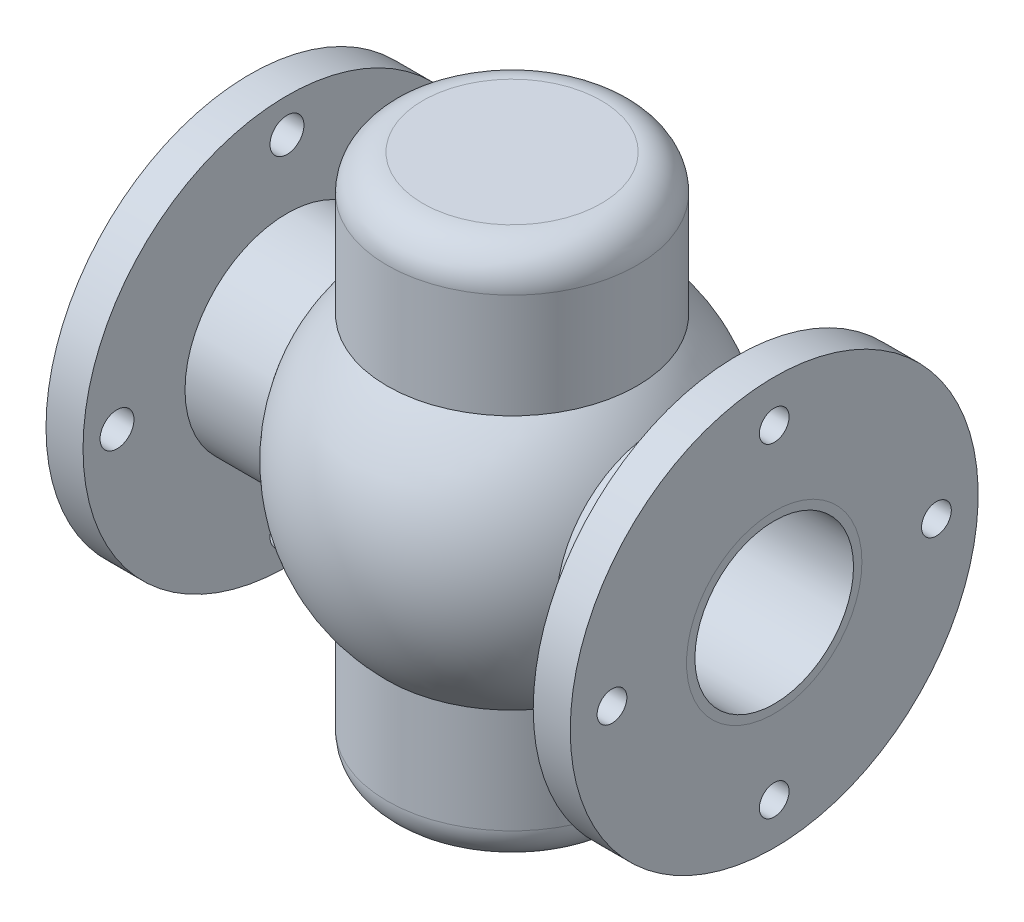
SolidWorks part; units mm, degrees
material "Cast Stainless Steel"
ref_plane "Front" through (0, 0, 0) normal (0, 0, 1) x (1, 0, 0)
ref_plane "Top" through (0, 0, 0) normal (0, 1, 0) x (1, 0, 0)
ref_plane "Right" through (0, 0, 0) normal (1, 0, 0) x (0, 0, -1)
other "Configuration Table"
sketch "Sketch1" plane through (0, 0, 0) normal (1, 0, 0) x (0, 0, -1)
  circle A0 centre (0, 0) radius 57.15
  dimension "D1" = 114.3
extrude "Base-Extrude" add sketch "Sketch1" along normal mid plane 300
sketch "Sketch2" plane through (0, 0, 0) normal (0, 1, 0) x (1, 0, 0)
  circle A0 centre (0, 0) radius 70
  dimension "D1" = 140
extrude "Boss-Extrude1" add sketch "Sketch2" along normal blind 150 and the other way blind 150
sketch "Sketch3" plane through (0, 0, 0) normal (0, 0, 1) x (1, 0, 0)
  line L0 (0, -115.863) -> (0, 215.6893) construction
  line L1 (0, 150) -> (0, -150) construction
  line L2 (0, -100) -> (0, 100)
  arc A0 (0, 100) -> (0, -100) centre (0, 0) cw
  dimension "D1" = 100
revolve "Boss-Revolve1" add sketch "Sketch3" angle 360 about L0
fillet "Fillet1" radius 20 2 edges at (0, -150, 70) (0, 150, 70)
shell "Shell1" [suppressed] thickness 10.5
sketch "Sketch18" plane through (-150, 0, 0) normal (-1, 0, 0) x (0, 0, 1)
  circle A0 centre (0, 0) radius 44.45
  dimension "D1" = 88.9
extrude "Cut-Extrude3" cut sketch "Sketch18" against normal through all
sketch "Sketch5" [suppressed] plane through (0, 0, 0) normal (0, 0, 1) x (1, 0, 0)
  line L0 (190, 198.3801) -> (180, 198.3801)
  line L1 (180, 198.3801) -> (180, 210)
  line L2 (180, 210) -> (185, 210)
  line L3 (180, 210) -> (-180, 210) construction
  line L4 (180, 160) -> (180, 210) construction
  line L5 (0, 0) -> (0, 105.4969) construction
  line L6 (0, 120) -> (0, 71.4143) construction
  arc A0 (190, 198.3801) -> (185, 210) centre (173.9977, 198.3801) ccw
  dimension "D1" = 16.0023
  dimension "D2" = 10
  dimension "D3" = 5
revolve "Boss-Revolve3" [suppressed] add sketch "Sketch5" angle 360 about L5
sketch "Sketch6" plane through (0, 150, 0) normal (0, 1, 0) x (-1, 0, 0)
  circle A0 centre (0, 0) radius 60
  dimension "D1" = 120
extrude "Boss-Extrude2" [suppressed] add sketch "Sketch6" along normal blind 30
sketch "Sketch7" [suppressed] plane through (0, 180, 0) normal (0, 1, 0) x (-1, 0, 0)
  circle A0 centre (0, 0) radius 50
  dimension "D1" = 100
extrude "Boss-Extrude3" [suppressed] add sketch "Sketch7" along normal blind 25
sketch "Sketch8" [suppressed] plane through (0, 205, 0) normal (0, 1, 0) x (-1, 0, 0)
  circle A0 centre (0, 0) radius 35
  dimension "D1" = 70
extrude "Boss-Extrude4" [suppressed] add sketch "Sketch8" along normal blind 10
sketch "Sketch9" [suppressed] plane through (0, 215, 0) normal (0, 1, 0) x (-1, 0, 0)
  circle A0 centre (0, 0) radius 12.5
  dimension "D1" = 25
extrude "Boss-Extrude5" [suppressed] add sketch "Sketch9" along normal blind 35
sketch "hexagon2" [suppressed] plane through (-2.3581, 250, -8.0849) normal (0, 1, 0) x (-1, 0, 0)
  line L0 (17.6378, 8.4916) -> (7.2876, 25.6052)
  line L1 (7.2876, 25.6052) -> (-12.7082, 25.1985)
  line L2 (-12.7082, 25.1985) -> (-22.354, 7.6782)
  line L3 (-22.354, 7.6782) -> (-12.0038, -9.4354)
  line L4 (-12.0038, -9.4354) -> (7.9921, -9.0287)
  line L5 (7.9921, -9.0287) -> (17.6378, 8.4916)
  circle A0 centre (-2.3581, 8.0849) radius 20 construction
  dimension "Outside Diameter" = 40
extrude "Boss-Extrude6" [suppressed] add sketch "hexagon2" against normal blind 15
sketch "Sketch13" plane through (0, 0, 0) normal (0, 0, 1) x (1, 0, 0)
  line L0 (0, 0) -> (246.3426, 0) construction
  line L1 (150, 0) -> (82.0602, 0) construction
  line L2 (126.15, 57.15) -> (126.15, 114.3)
  line L3 (126.15, 114.3) -> (146.9, 114.3)
  line L4 (146.9, 114.3) -> (146.9, 67.5)
  line L5 (146.9, 67.5) -> (150, 67.5)
  line L6 (150, 67.5) -> (150, 57.15)
  line L7 (150, 57.15) -> (126.15, 57.15)
  line L8 (150, 57.15) -> (82.0602, 57.15) construction
  line L9 (150, -57.15) -> (150, 57.15) construction
  dimension "D1" = 114.3
  dimension "D2" = 67.5
  dimension "D3" = 20.75
  dimension "D4" = 3.1
revolve "Boss-Revolve4" add sketch "Sketch13" angle 360 about L0
mirror "Mirror2" about plane through (0, 0, 0) normal (1, 0, 0) of "Boss-Revolve4"
sketch "Sketch14" plane through (146.9, 0, 0) normal (1, 0, 0) x (0, 0, -1)
  line L1 (0, 0) -> (0, 114.3) construction
  line L2 (0, 0) -> (0, 95.25) construction
  circle A0 centre (0, 95.25) radius 9.5
  circle A1 centre (0, 0) radius 114.3 construction
  dimension "D1" = 19
  dimension "D2" = 95.25
  dimension "D3" = 0
extrude "Cut-Extrude1" [suppressed] cut sketch "Sketch14" against normal up to next
pattern_circular "CirPattern1" [suppressed] count 4 over 360 about axis through (0, 0, 0) along (1, 0, 0)
sketch "Sketch15" plane through (-146.9, 0, 0) normal (-1, 0, 0) x (0, 0, 1)
  line L0 (0, 0) -> (0, 62.7443) construction
  line L1 (0, 0) -> (0, 95.25) construction
  circle A1 centre (0, 95.25) radius 9.5
  circle A2 centre (0, 0) radius 95.25 construction
  dimension "D1" = 19
  dimension "D2" = 190.5
  dimension "D3" = 0
extrude "Cut-Extrude2" cut sketch "Sketch15" against normal up to next
pattern_circular "CirPattern2" count 4 over 360 about axis through (0, 0, 0) along (1, 0, 0) of "Cut-Extrude2"
sketch "Sketch22" plane through (146.9, 0, 0) normal (1, 0, 0) x (0, 0, -1)
  circle A0 centre (0, 0) radius 67.5 construction
  circle A1 centre (0, 0) radius 67.5
extrude "Cut-Extrude5" cut sketch "Sketch22" along normal up to surface (3.1 mm away) up to face at (150, 0, 44.45)
sketch "Sketch24" plane through (146.9, 0, 0) normal (1, 0, 0) x (0, 0, -1)
  circle A0 centre (0, 0) radius 49.15
  circle A7 centre (0, 0) radius 49.15 construction
split line "Split Line1"
hole_wizard "5/8 Clearance Hole1" positions "Sketch25" profile "Sketch26" hole size "5/8" standard "Ansi Inch" end condition through all
sketch "Sketch25" plane through (126.15, -86.9453, 61.2299) normal (-1, 0, 0) x (0, 0, 1)
  line L0 (-61.2299, 86.9453) -> (160.2598, 86.9453) construction
  line L1 (-61.2299, 86.9453) -> (-61.2299, 296.6144) construction
  line L2 (-61.2299, 86.9453) -> (-291.9631, 86.9453) construction
  line L3 (-61.2299, 86.9453) -> (-61.2299, -121.1078) construction
  circle A0 centre (-61.2299, 86.9453) radius 90.9114 construction
  point P0 (-61.2299, 177.798)
  point P1 (29.6815, 86.9453)
  point P2 (-61.2299, -3.9661)
  point P3 (-152.1413, 86.9453)
sketch "Sketch26" plane through (126.15, 90.8528, 0) normal (0, 1, 0) x (0, 0, 1)
  line L0 (0, 0) -> (0, 20.75)
  line L1 (0, 20.75) -> (8.3337, 20.75)
  line L2 (8.3337, 20.75) -> (8.3337, 0)
  line L5 (8.3337, 0) -> (0, 0)
  line L11 (0, -6.35) -> (0, 107.95) construction
  dimension "Thru Hole Dia." = 16.6675
  dimension "Thru Hole Depth" = 20.75
